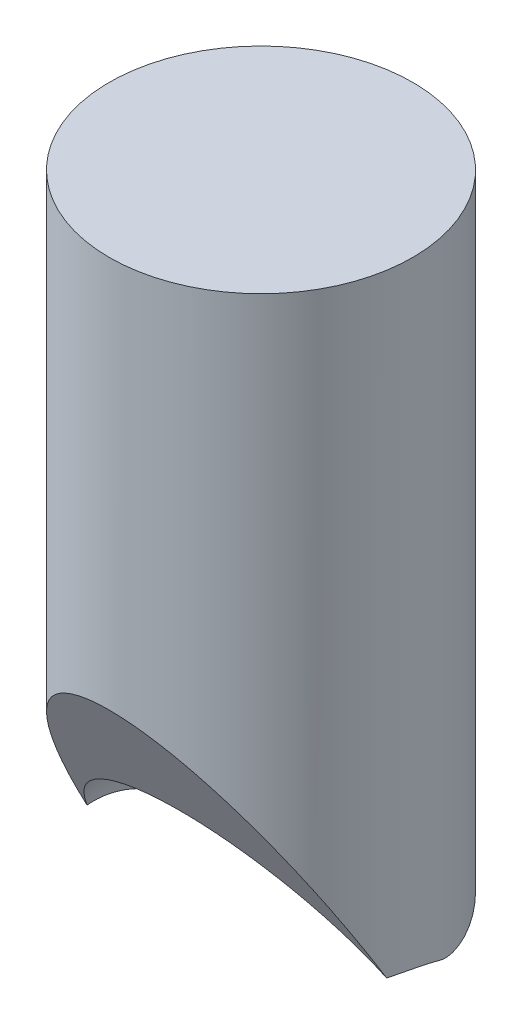
SolidWorks part; units mm, degrees
ref_plane "Front Plane" through (0, 0, 0) normal (0, 0, 1) x (1, 0, 0)
ref_plane "Top Plane" through (0, 0, 0) normal (0, 1, 0) x (1, 0, 0)
ref_plane "Right Plane" through (0, 0, 0) normal (1, 0, 0) x (0, 0, -1)
sketch "Sketch1" plane through (0, 0, 0) normal (0, 1, 0) x (1, 0, 0)
  circle A0 centre (0, 0) radius 40
  dimension "D2" = 80
extrude "Boss-Extrude1" add sketch "Sketch1" along normal blind 200
sketch "Sketch4" plane through (0, 0, 0) normal (1, 0, 0) x (0, 0, -1)
  line L0 (-40, 96.6484) -> (15.8, 0)
  line L2 (-40, 120) -> (-40, 20) construction
  line L3 (-40, 0) -> (40, 0) construction
  line L4 (15.8, 0) -> (-40, 0)
  line L5 (-40, 0) -> (-40, 96.6484)
  dimension "D1" = 120
  dimension "D2" = 55.8
extrude "Cut-Extrude2" cut sketch "Sketch4" against normal through all both and the other way through all
ref_plane "Plane2" through (0, 23.0973, 13.3353) normal (0, -0.866, -0.5) x (1, 0, 0)
sketch "Sketch5" plane through (0, 23.0973, 13.3353) normal (0, -0.866, -0.5) x (1, 0, 0)
  circle A0 centre (0, -12.4345) radius 41
  arc A1 (-38.7298, -2.4345) -> (38.7298, -2.4345) centre (0, -12.4345) ccw construction
  dimension "D1" = 1
extrude "Cut-Extrude4" cut sketch "Sketch5" along normal through all
sketch "Sketch8" plane through (0, 23.0973, 13.3353) normal (0, -0.866, -0.5) x (1, 0, 0)
  line L1 (40.981, -13.6832) -> (-40.981, -13.6832)
  line L2 (39.9724, -13.6832) -> (-39.9724, -13.6832) construction
  arc A0 (-40.981, -13.6832) -> (40.981, -13.6832) centre (0, -12.4345) ccw
  arc A1 (-39.256, -24.2654) -> (39.256, -24.2654) centre (0, -12.4345) ccw construction
revolve "Cut-Revolve5" cut sketch "Sketch8" angle 360 about L1
